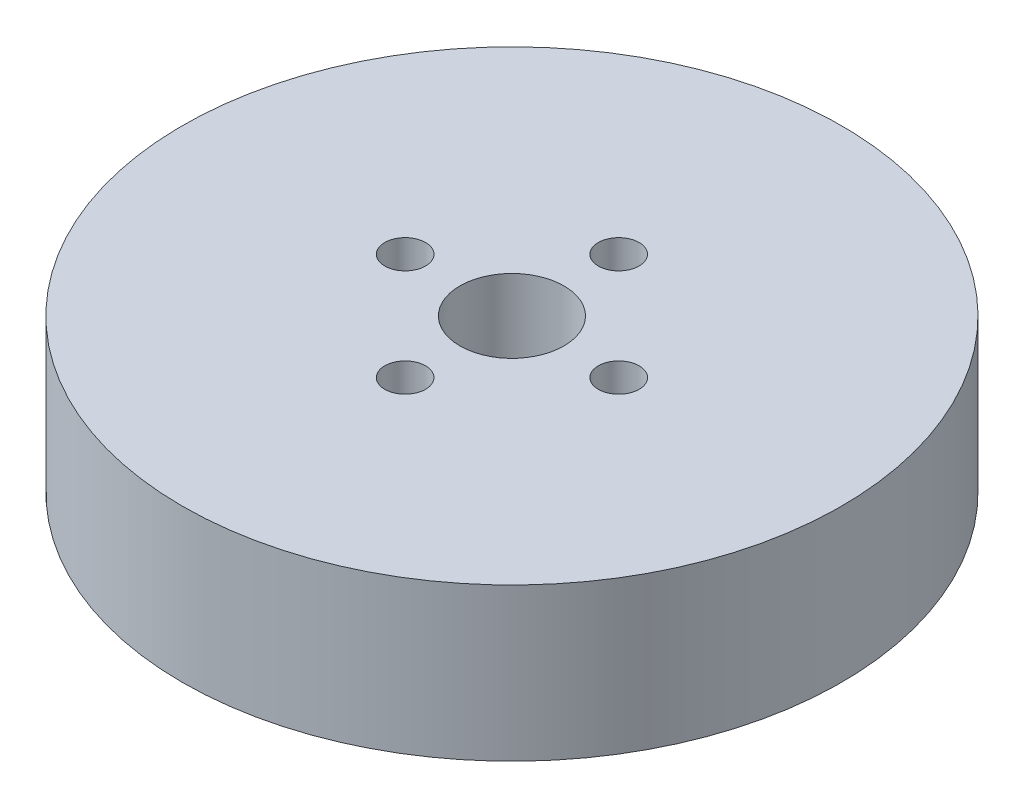
SolidWorks part; units mm, degrees
ref_plane "Front Plane" through (0, 0, 0) normal (0, 0, 1) x (1, 0, 0)
ref_plane "Top Plane" through (0, 0, 0) normal (0, 1, 0) x (1, 0, 0)
ref_plane "Right Plane" through (0, 0, 0) normal (1, 0, 0) x (0, 0, -1)
sketch "Sketch1" plane through (0, 0, 0) normal (0, 1, 0) x (1, 0, 0)
  circle A0 centre (0, 0) radius 47.5
  dimension "FLANGE_OD" = 95
extrude "Boss-Extrude1" add sketch "Sketch1" along normal blind 22
sketch "Sketch2" plane through (0, 0, 0) normal (0, 1, 0) x (1, 0, 0)
  circle A0 centre (0, 0) radius 7.5
  dimension "BORE_D" = 15
extrude "Cut-Extrude1" cut sketch "Sketch2" along normal through all
sketch "Sketch3" plane through (0, 22, 0) normal (0, 1, 0) x (1, 0, 0)
  circle A0 centre (0, 0) radius 15.3893 construction
  circle A1 centre (-15.3893, 0) radius 2.9413
  dimension "BOLT_D" = 5.8825
  dimension "BOLT_PCD" = 30.7786
extrude "Cut-Extrude2" cut sketch "Sketch3" against normal blind 17.2224
pattern_circular "CirPattern1" count 4 over 360 about axis through (0, 0, 0) along (0, 1, 0) of "Cut-Extrude2"
